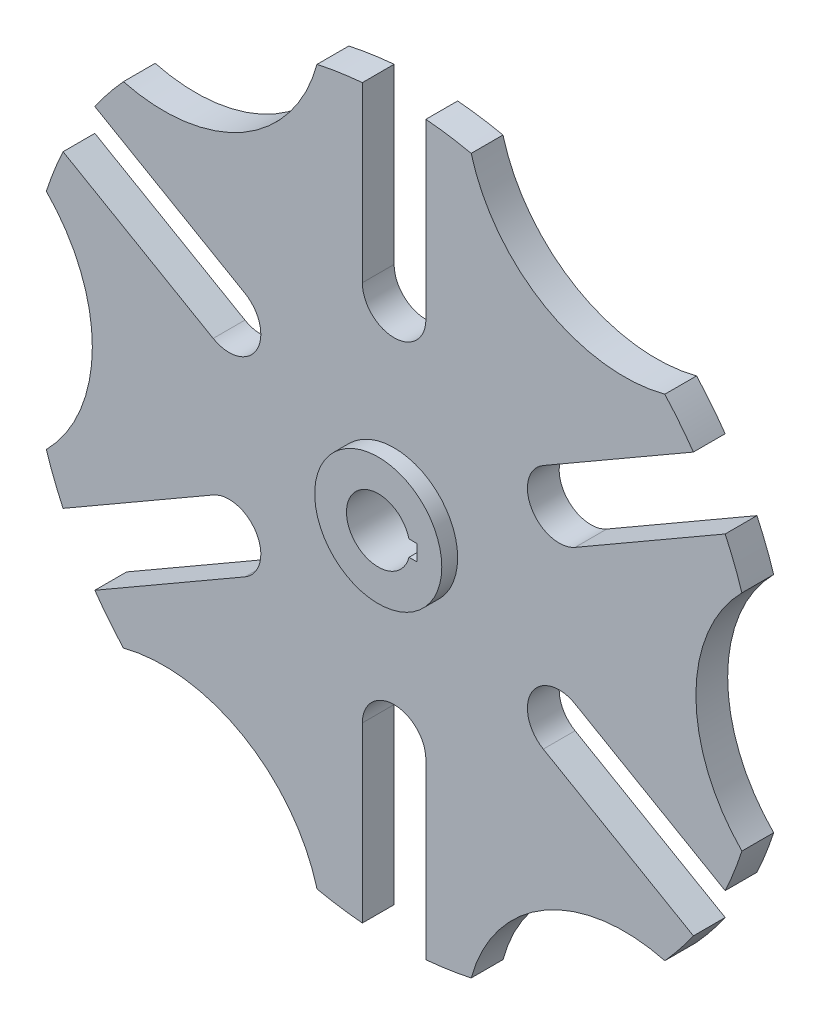
SolidWorks part; units mm, degrees
material "1060 Alloy"
ref_plane "Front Plane" through (0, 0, 0) normal (0, 0, 1) x (1, 0, 0)
ref_plane "Top Plane" through (0, 0, 0) normal (0, 1, 0) x (1, 0, 0)
ref_plane "Right Plane" through (0, 0, 0) normal (1, 0, 0) x (0, 0, -1)
sketch "Sketch3" plane through (0, 0, 0) normal (0, 0, 1) x (1, 0, 0)
  circle A3 centre (0, 0) radius 73.025
  dimension "D1" = 146.05
extrude "Boss-Extrude2" add sketch "Sketch3" along normal mid plane 6.35
sketch "Sketch5" plane through (0, 0, 3.175) normal (0, 0, 1) x (1, 0, 0)
  line L0 (0, 76.9841) -> (0, -79.3993) construction
  line L1 (-99.9284, 0) -> (101.5386, 0) construction
  line L2 (0, 0) -> (95.0773, 54.8929) construction
  line L3 (63.002, 36.3742) -> (32.9956, 19.05) construction
  line L4 (66.177, 30.8749) -> (36.1706, 13.5507)
  line L5 (59.827, 41.8735) -> (29.8206, 24.5493)
  line L6 (63.002, -36.3742) -> (32.9956, -19.05) construction
  line L7 (59.827, -41.8735) -> (29.8206, -24.5493)
  line L8 (66.177, -30.8749) -> (36.1706, -13.5507)
  line L9 (0, -72.7484) -> (0, -38.1) construction
  line L10 (-6.35, -72.7484) -> (-6.35, -38.1)
  line L11 (6.35, -72.7484) -> (6.35, -38.1)
  line L12 (-63.002, -36.3742) -> (-32.9956, -19.05) construction
  line L13 (-66.177, -30.8749) -> (-36.1706, -13.5507)
  line L14 (-59.827, -41.8735) -> (-29.8206, -24.5493)
  line L15 (-63.002, 36.3742) -> (-32.9956, 19.05) construction
  line L16 (-59.827, 41.8735) -> (-29.8206, 24.5493)
  line L17 (-66.177, 30.8749) -> (-36.1706, 13.5507)
  line L18 (0, 72.7484) -> (0, 38.1) construction
  line L19 (6.35, 72.7484) -> (6.35, 38.1)
  line L20 (-6.35, 72.7484) -> (-6.35, 38.1)
  circle A0 centre (0, 0) radius 38.1 construction
  circle A1 centre (92.075, 0) radius 31.75
  arc A2 (66.177, 30.8749) -> (59.827, 41.8735) centre (63.002, 36.3742) ccw
  arc A3 (29.8206, 24.5493) -> (36.1706, 13.5507) centre (32.9956, 19.05) ccw
  circle A4 centre (0, 0) radius 73.025 construction
  circle A5 centre (46.0375, -79.7393) radius 31.75
  arc A6 (59.827, -41.8735) -> (66.177, -30.8749) centre (63.002, -36.3742) ccw
  arc A7 (36.1706, -13.5507) -> (29.8206, -24.5493) centre (32.9956, -19.05) ccw
  circle A8 centre (-46.0375, -79.7393) radius 31.75
  arc A9 (-6.35, -72.7484) -> (6.35, -72.7484) centre (0, -72.7484) ccw
  arc A10 (6.35, -38.1) -> (-6.35, -38.1) centre (0, -38.1) ccw
  circle A11 centre (-92.075, 0) radius 31.75
  arc A12 (-66.177, -30.8749) -> (-59.827, -41.8735) centre (-63.002, -36.3742) ccw
  arc A13 (-29.8206, -24.5493) -> (-36.1706, -13.5507) centre (-32.9956, -19.05) ccw
  circle A14 centre (-46.0375, 79.7393) radius 31.75
  arc A15 (-59.827, 41.8735) -> (-66.177, 30.8749) centre (-63.002, 36.3742) ccw
  arc A16 (-36.1706, 13.5507) -> (-29.8206, 24.5493) centre (-32.9956, 19.05) ccw
  circle A17 centre (46.0375, 79.7393) radius 31.75
  arc A18 (6.35, 72.7484) -> (-6.35, 72.7484) centre (0, 72.7484) ccw
  arc A19 (-6.35, 38.1) -> (6.35, 38.1) centre (0, 38.1) ccw
  point P12 (47.9988, 27.7121)
  point P25 (47.9988, -27.7121)
  point P34 (0, -55.4242)
  point P43 (-47.9988, -27.7121)
  point P52 (-47.9988, 27.7121)
  point P61 (0, 55.4242)
  point P66 (0, 0)
  dimension "D2" = 76.2
  dimension "D3" = 63.5
  dimension "D1" = 30
  dimension "D4" = 92.075
  dimension "D5" = 12.7
  dimension "D6" = 6
extrude "Cut-Extrude3" cut sketch "Sketch5" against normal through all
sketch "Sketch7" plane through (0, 0, 3.175) normal (0, 0, 1) x (1, 0, 0)
  line L1 (6.1484, 1.5875) -> (7.7359, 1.5875)
  line L3 (6.1484, -1.5875) -> (7.7359, -1.5875)
  line L4 (7.7359, 1.5875) -> (7.7359, -1.5875)
  circle A0 centre (0, 0) radius 12.7
  arc A1 (6.1484, 1.5875) -> (6.1484, -1.5875) centre (0, 0) ccw
  point P4 (6.35, 0)
  point P11 (7.7359, 0)
  dimension "D1" = 25.4
  dimension "D2" = 12.7
  dimension "D3" = 1.5875
  dimension "D4" = 3.175
extrude "Cut-Extrude4" cut sketch "Sketch7" against normal through all contours L3 L4 L1 A1
extrude "Boss-Extrude4" add sketch "Sketch7<3>" along normal blind 3.175
sketch "Sketch7<3>" plane through (0, 0, 3.175) normal (0, 0, 1) x (1, 0, 0) same geometry as "Sketch7"
